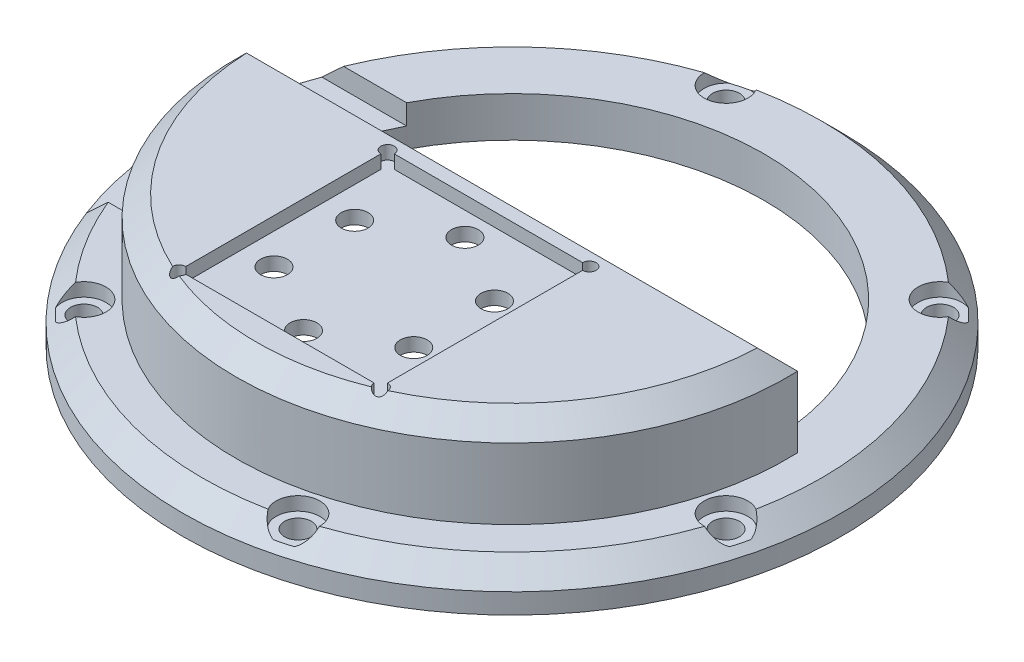
SolidWorks part; units mm, degrees
other "마크업1"
sketch "스케치15" plane through (49, 0, -49) normal (0.8815, -0.0728, -0.4665) x (-0.4667, 0.0147, -0.8843)
material "6061 합금"
ref_plane "정면" through (0, 0, 0) normal (0, 0, 1) x (1, 0, 0)
ref_plane "윗면" through (0, 0, 0) normal (0, 1, 0) x (1, 0, 0)
ref_plane "우측면" through (0, 0, 0) normal (1, 0, 0) x (0, 0, -1)
sketch "스케치1" plane through (0, 0, 0) normal (0, 1, 0) x (1, 0, 0)
  line L0 (-43.4667, 11.6469) -> (0, 0) construction
  line L1 (0, 0) -> (-45, 0) construction
  circle A0 centre (0, 0) radius 45
  circle A1 centre (0, 0) radius 49
  circle A2 centre (0, 0) radius 37.5
  circle A3 centre (-43.4667, 11.6469) radius 2
  circle A4 centre (-11.6469, 43.4667) radius 2
  circle A5 centre (31.8198, 31.8198) radius 2
  circle A6 centre (43.4667, -11.6469) radius 2
  circle A7 centre (11.6469, -43.4667) radius 2
  circle A8 centre (-31.8198, -31.8198) radius 2
  point P7 (0, 0)
  point P9 (0, 0)
  point P20 (0, 0)
  point P21 (-45, 10.6661)
  dimension "D1" = 75
  dimension "D2" = 98
  dimension "D3" = 90
  dimension "D4" = 4
  dimension "D5" = 15
  dimension "D6" = 6
extrude "보스-돌출1" add sketch "스케치1" along normal blind 15.5 contours A8 A0 A7 A6 A5 A4 A3 A2 | A1 A8 A0 A3 A4 A5 A6 A7 region at (43.4692, 0, 4.7427) region at (-47.6141, 0, 0)
extrude "보스-돌출2" add sketch "스케치1<3>" along normal blind 4 from surface contours A2 | A8 A0 A7 A6 A5 A4 A3 A2 | A1 A8 A0 A3 A4 A5 A6 A7 region at (43.4692, 0, 4.7427) region at (-47.6141, 0, 0) region at (0, 0, 0) starting at face at (11.6469, 15.5, 45.4667)
sketch "스케치1<3>" plane through (0, 0, 0) normal (0, 1, 0) x (1, 0, 0) same geometry as "스케치1"
sketch "스케치2" plane through (0, 19.5, 0) normal (0, 1, 0) x (1, 0, 0)
  line L1 (-64.8338, -17.5) -> (-33.1662, -17.5)
  line L2 (-64.8338, -17.5) -> (-64.8338, 17.5)
  line L3 (-64.8338, 17.5) -> (-33.1662, 17.5)
  line L4 (-33.1662, -17.5) -> (-33.1662, 17.5)
  line L5 (-64.8338, -17.5) -> (-33.1662, 17.5) construction
  line L6 (-64.8338, 17.5) -> (-33.1662, -17.5) construction
  circle A0 centre (0, 0) radius 49 construction
  circle A1 centre (0, 0) radius 37.5 construction
  point P0 (-49, 0)
  point P7 (0, 0)
  point P9 (0, 0)
  point P10 (0, 0)
  point P11 (0, 0)
  point P12 (0, 0)
  dimension "D1" = 35
extrude "컷-돌출1" cut sketch "스케치2" against normal blind 8.5 from offset 8 offset against normal yes
sketch "스케치3" [suppressed] plane through (0, 0, 0) normal (1, 0, 0) x (0, 0, -1)
  line L0 (49, 22.5) -> (-49, 22.5) construction
  line L1 (-1.5, 25.5) -> (1.5, 25.5)
  line L2 (-1.5, 25.5) -> (-1.5, 19.5)
  line L3 (-1.5, 19.5) -> (1.5, 19.5)
  line L4 (1.5, 25.5) -> (1.5, 19.5)
  line L5 (-1.5, 25.5) -> (1.5, 19.5) construction
  line L6 (-1.5, 19.5) -> (1.5, 25.5) construction
  line L7 (3.5, 25.5) -> (6.5, 25.5)
  line L8 (6.5, 25.5) -> (6.5, 19.5)
  line L9 (3.5, 25.5) -> (3.5, 19.5)
  line L10 (3.5, 19.5) -> (6.5, 19.5)
  line L11 (8.5, 25.5) -> (11.5, 25.5)
  line L12 (11.5, 25.5) -> (11.5, 19.5)
  line L13 (8.5, 25.5) -> (8.5, 19.5)
  line L14 (8.5, 19.5) -> (11.5, 19.5)
  line L15 (13.5, 25.5) -> (16.5, 25.5)
  line L16 (16.5, 25.5) -> (16.5, 19.5)
  line L17 (13.5, 25.5) -> (13.5, 19.5)
  line L18 (13.5, 19.5) -> (16.5, 19.5)
  line L19 (18.5, 25.5) -> (21.5, 25.5)
  line L20 (21.5, 25.5) -> (21.5, 19.5)
  line L21 (18.5, 25.5) -> (18.5, 19.5)
  line L22 (18.5, 19.5) -> (21.5, 19.5)
  line L23 (23.5, 25.5) -> (26.5, 25.5)
  line L24 (26.5, 25.5) -> (26.5, 19.5)
  line L25 (23.5, 25.5) -> (23.5, 19.5)
  line L26 (23.5, 19.5) -> (26.5, 19.5)
  line L27 (28.5, 25.5) -> (31.5, 25.5)
  line L28 (31.5, 25.5) -> (31.5, 19.5)
  line L29 (28.5, 25.5) -> (28.5, 19.5)
  line L30 (28.5, 19.5) -> (31.5, 19.5)
  line L31 (33.5, 25.5) -> (36.5, 25.5)
  line L32 (36.5, 25.5) -> (36.5, 19.5)
  line L33 (33.5, 25.5) -> (33.5, 19.5)
  line L34 (33.5, 19.5) -> (36.5, 19.5)
  line L35 (-6.5, 25.5) -> (-3.5, 25.5)
  line L36 (-3.5, 25.5) -> (-3.5, 19.5)
  line L37 (-6.5, 25.5) -> (-6.5, 19.5)
  line L38 (-6.5, 19.5) -> (-3.5, 19.5)
  line L39 (-11.5, 25.5) -> (-8.5, 25.5)
  line L40 (-8.5, 25.5) -> (-8.5, 19.5)
  line L41 (-11.5, 25.5) -> (-11.5, 19.5)
  line L42 (-11.5, 19.5) -> (-8.5, 19.5)
  line L43 (-16.5, 25.5) -> (-13.5, 25.5)
  line L44 (-13.5, 25.5) -> (-13.5, 19.5)
  line L45 (-16.5, 25.5) -> (-16.5, 19.5)
  line L46 (-16.5, 19.5) -> (-13.5, 19.5)
  line L47 (-21.5, 25.5) -> (-18.5, 25.5)
  line L48 (-18.5, 25.5) -> (-18.5, 19.5)
  line L49 (-21.5, 25.5) -> (-21.5, 19.5)
  line L50 (-21.5, 19.5) -> (-18.5, 19.5)
  line L51 (-26.5, 25.5) -> (-23.5, 25.5)
  line L52 (-23.5, 25.5) -> (-23.5, 19.5)
  line L53 (-26.5, 25.5) -> (-26.5, 19.5)
  line L54 (-26.5, 19.5) -> (-23.5, 19.5)
  line L55 (-31.5, 25.5) -> (-28.5, 25.5)
  line L56 (-28.5, 25.5) -> (-28.5, 19.5)
  line L57 (-31.5, 25.5) -> (-31.5, 19.5)
  line L58 (-31.5, 19.5) -> (-28.5, 19.5)
  line L59 (-36.5, 25.5) -> (-33.5, 25.5)
  line L60 (-33.5, 25.5) -> (-33.5, 19.5)
  line L61 (-36.5, 25.5) -> (-36.5, 19.5)
  line L62 (-36.5, 19.5) -> (-33.5, 19.5)
  point P0 (0, 22.5)
  dimension "D1" = 3
  dimension "D2" = 3
  dimension "D5" = 5
  dimension "D6" = 5
  dimension "D3" = 8
  dimension "D4" = 8
sketch "스케치4" plane through (0, 19.5, 0) normal (0, 1, 0) x (1, 0, 0)
  circle A0 centre (-11.6469, 43.4667) radius 3.25
  circle A1 centre (0, 0) radius 45
  circle A2 centre (31.8198, 31.8198) radius 3.25
  circle A3 centre (43.4667, -11.6469) radius 3.25
  circle A4 centre (11.6469, -43.4667) radius 3.25
  circle A5 centre (-31.8198, -31.8198) radius 3.25
  circle A6 centre (-43.4667, 11.6469) radius 3.25
  point P7 (0, 0)
  point P8 (0, 0)
  point P18 (0, 0)
  circle M4 centre (-11.6469, 43.4667) radius 2
  circle M17 centre (43.4667, -11.6469) radius 2
  circle M18 centre (-31.8198, -31.8198) radius 2
  circle M19 centre (-43.4667, 11.6469) radius 2
  circle M20 centre (31.8198, 31.8198) radius 2
  circle M21 centre (11.6469, -43.4667) radius 2
  dimension "D2" = 6.5
  dimension "D1" = 6
extrude "컷-돌출3" cut sketch "스케치4" against normal blind 15.5 contours A1 A0 M4 | A0 A1 M4 | A1 M4 | A1 M4 | A1 M19 | A1 M19 | A1 A6 M19 | A1 A6 M19 | A1 M20 | A1 M20 | A1 A2 M20 | A1 A2 M20 | A1 A3 M17 | A1 M17 | A1 M17 | A1 A3 M17 | A1 A5 M18 | A1 M18 | A1 M18 | A1 A5 M18 | A1 A4 M21 | A1 M21 | A1 M21 | A1 A4 M21 region at (-11.1757, 19.5, -40.3268) region at (-9.108, 19.5, -44.147) region at (32.98, 19.5, -34.7703) region at (29.8589, 19.5, -33.5633) region at (-11.4251, 19.5, -42.6391) region at (-11.8645, 19.5, -44.2788) region at (-40.9133, 19.5, -13.5339) region at (-42.7864, 19.5, -14.1857) region at (32.4143, 19.5, -32.4143) region at (31.214, 19.5, -31.214) region at (-42.6391, 19.5, -11.4251) region at (-44.2788, 19.5, -11.8645) region at (-30.5529, 19.5, 28.911) region at (-33.6806, 19.5, 29.9632) region at (45.9489, 19.5, 9.6699) region at (43.9984, 19.5, 9.0774) region at (-31.214, 19.5, 31.214) region at (-32.4143, 19.5, 32.4143) region at (44.2788, 19.5, 11.8645) region at (42.6391, 19.5, 11.4251) region at (10.8251, 19.5, 40.3998) region at (9.108, 19.5, 44.147) region at (11.4251, 19.5, 42.6391) region at (11.8645, 19.5, 44.2788)
sketch "스케치6" plane through (0, 19.5, 0) normal (0, 1, 0) x (1, 0, 0)
  circle A0 centre (0, 0) radius 49
  circle A1 centre (0, 0) radius 41
  point P2 (-54.9192, 1.5)
  point P4 (0, 0)
  point P5 (0, 0)
  point P6 (0, 0)
  point P7 (27.2552, 1.5)
  point P13 (0, 0)
  dimension "D1" = 98
  dimension "D2" = 82
extrude "컷-돌출7" cut sketch "스케치6" against normal blind 13.5
sketch "스케치7" plane through (0, 19.5, 0) normal (0, 1, 0) x (1, 0, 0)
  line L1 (-15, -34.5) -> (15, -34.5)
  line L2 (-15, -34.5) -> (-15, -3.5)
  line L4 (15, -34.5) -> (15, -3.5)
  line L5 (-15, -34.5) -> (15, -3.5) construction
  line L6 (-15, -3.5) -> (15, -34.5) construction
  line L7 (-15, -3.5) -> (15, -3.5)
  point P0 (0, -19)
  dimension "D1" = 31
  dimension "D2" = 30
  dimension "D3" = 19
sketch "스케치8" plane through (0, 19.5, 0) normal (0, 1, 0) x (1, 0, 0)
  circle A0 centre (0, -19) radius 12
  circle A1 centre (0, -7) radius 2
  circle A2 centre (10.3923, -13) radius 2
  circle A3 centre (10.3923, -25) radius 2
  circle A4 centre (0, -31) radius 2
  circle A5 centre (-10.3923, -25) radius 2
  circle A6 centre (-10.3923, -13) radius 2
  point P6 (0, 0)
  point P7 (0, 0)
  point P17 (0, -19)
  point P18 (0, 0)
  point P19 (0, 0)
  point P20 (-0.2726, -5.6554)
  point P22 (0, 0)
  dimension "D1" = 24
  dimension "D2" = 4
  dimension "D3" = 6
extrude "컷-돌출9" cut sketch "스케치8" against normal blind 16.5 contours A0 A1 | A0 A1 | A0 A6 | A0 A6 | A0 A2 | A0 A2 | A0 A5 | A0 A5 | A0 A4 | A0 A4 | A0 A3 | A0 A3 region at (9.6318, 19.5, 13.4391) region at (11.1008, 19.5, 12.5909) region at (11.1008, 19.5, 25.4091) region at (9.6318, 19.5, 24.5609) region at (0, 19.5, 7.8781) region at (0, 19.5, 6.1819) region at (0, 19.5, 31.8181) region at (0, 19.5, 30.1219) region at (-9.6318, 19.5, 13.4391) region at (-11.1008, 19.5, 12.5909) region at (-11.1008, 19.5, 25.4091) region at (-9.6318, 19.5, 24.5609)
sketch "스케치9" plane through (0, 15.5, 0) normal (0, -1, 0) x (1, 0, 0)
  circle A0 centre (0, 31) radius 3.25
  circle A1 centre (10.3923, 25) radius 3.25
  circle A2 centre (10.3923, 13) radius 3.25
  circle A3 centre (0, 7) radius 3.25
  circle A4 centre (-10.3923, 13) radius 3.25
  circle A5 centre (-10.3923, 25) radius 3.25
  circle A6 centre (0, 19) radius 12 construction
  point P4 (0, 0)
  point P15 (0, 19)
  point P17 (0, 0)
  dimension "D1" = 6.5
  dimension "D2" = 6
extrude "컷-돌출10" [suppressed] cut sketch "스케치9" against normal blind 4
extrude "컷-돌출11" cut sketch "스케치7" against normal blind 2
sketch "스케치10" plane through (0, 19.5, 0) normal (0, 1, 0) x (1, 0, 0)
  circle A0 centre (-15, -3.5) radius 1
  circle A1 centre (15, -3.5) radius 1
  circle A2 centre (15, -34.5) radius 1
  circle A3 centre (-15, -34.5) radius 1
  point P12 (0, 0)
  point P13 (16.7093, 0)
  point P15 (0, 0)
  point P16 (-20.1831, -31.8242)
  point P18 (0, 0)
  point P19 (23.6661, -31.7595)
  point P20 (0, 0)
  point P21 (-21.2825, -3.5)
  point P22 (0, 0)
  dimension "D1" = 2
extrude "컷-돌출13" cut sketch "스케치10" against normal blind 2
sketch "스케치12" plane through (0, 19.5, 0) normal (0, 1, 0) x (1, 0, 0)
  line L0 (14, -3.5) -> (-14, -3.5) construction
  line L1 (-45.7684, 49) -> (49, 49)
  line L2 (-45.7684, 49) -> (-45.7684, 1.5)
  line L3 (-45.7684, 1.5) -> (49, 1.5)
  line L4 (49, 49) -> (49, 1.5)
  arc A1 (-45.7684, -17.5) -> (-45.7684, 17.5) centre (0, 0) ccw construction
  dimension "D1" = 5
extrude "컷-돌출14" cut sketch "스케치12" against normal blind 13.5
chamfer "모따기1" distance 3 angle 45 1 edges at (0, 19.5, -1.5)
chamfer "모따기2" distance 3 angle 45 1 edges at (49, 6, 0)
chamfer "모따기3" distance 3 angle 45 1 edges at (0, 19.5, 41)
